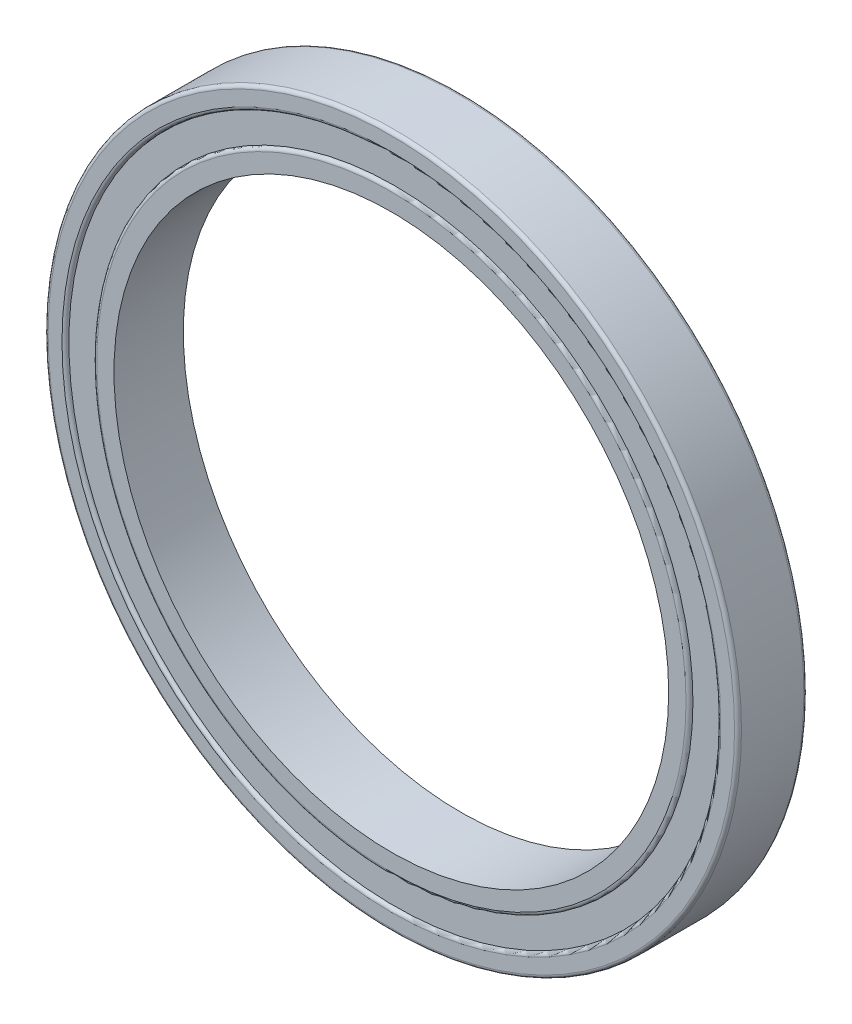
SolidWorks part; units mm, degrees
ref_plane "Front Plane" through (0, 0, 0) normal (0, 0, 1) x (1, 0, 0)
ref_plane "Top Plane" through (0, 0, 0) normal (0, 1, 0) x (1, 0, 0)
ref_plane "Right Plane" through (0, 0, 0) normal (1, 0, 0) x (0, 0, -1)
sketch "Sketch1" plane through (0, 0, 0) normal (0, 0, 1) x (1, 0, 0)
  circle A0 centre (0, 0) radius 40
  circle A1 centre (0, 0) radius 50
  dimension "D1" = 80
  dimension "D2" = 100
extrude "Boss-Extrude1" add sketch "Sketch1" along normal blind 10
sketch "Sketch2" plane through (0, 0, 10) normal (0, 0, 1) x (1, 0, 0)
  circle A0 centre (0, 0) radius 47
  circle A1 centre (0, 0) radius 43
  circle A2 centre (0, 0) radius 50 construction
  circle A3 centre (0, 0) radius 40 construction
  dimension "D1" = 3
  dimension "D2" = 3
extrude "Cut-Extrude1" cut sketch "Sketch2" against normal blind 0.5
sketch "Sketch3" plane through (0, 0, 0) normal (0, 0, -1) x (-1, 0, 0)
  circle A0 centre (0, 0) radius 43
  circle A1 centre (0, 0) radius 47
  circle A2 centre (0, 0) radius 50 construction
  circle A3 centre (0, 0) radius 40 construction
  dimension "D1" = 3
  dimension "D2" = 3
extrude "Cut-Extrude2" cut sketch "Sketch3" against normal blind 0.5
fillet "Fillet1" radius 0.5 6 edges at (-43, 0, 0) (-47, 0, 0) (43, 0, 10) (47, 0, 10) (50, 0, 0) (50, 0, 10)
